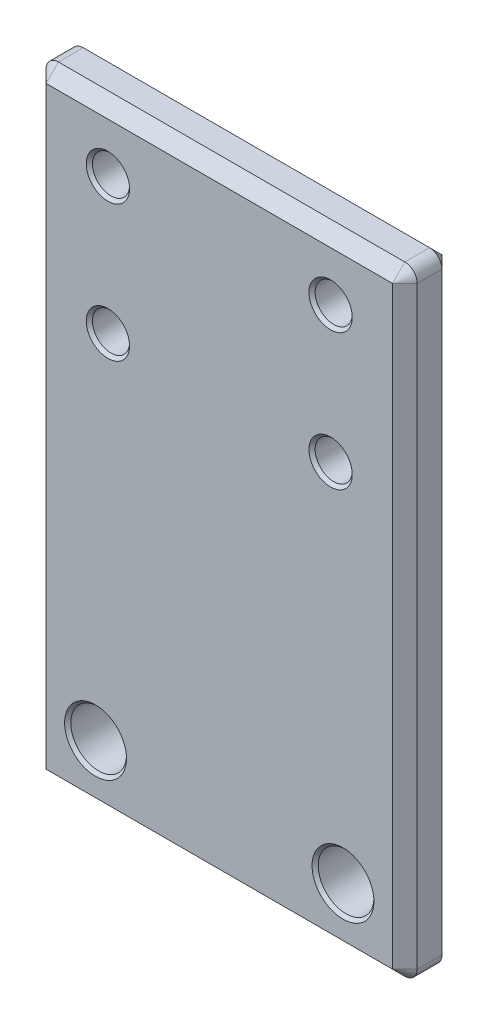
SolidWorks part; units mm, degrees
material "ABS"
ref_plane "Front Plane" through (0, 0, 0) normal (0, 0, 1) x (1, 0, 0)
ref_plane "Top Plane" through (0, 0, 0) normal (0, 1, 0) x (1, 0, 0)
ref_plane "Right Plane" through (0, 0, 0) normal (1, 0, 0) x (0, 0, -1)
ref_axis "X Axis" through (88.99, 0, 0) along (-1, 0, 0)
ref_axis "Y Axis" through (0, 55, 0) along (0, -1, 0)
ref_axis "Z Axis" through (0, 0, -88.99) along (0, 0, 1)
sketch "Sketch1" plane through (0, 0, 0) normal (0, 0, 1) x (1, 0, 0)
  line L1 (-15, -39.5) -> (15, -39.5)
  line L2 (-15, -39.5) -> (-15, 10.5)
  line L3 (-15, 10.5) -> (15, 10.5)
  line L4 (15, -39.5) -> (15, 10.5)
  line L5 (0, 10.5) -> (0, -39.5) construction
  line L6 (-15, -14.5) -> (15, -14.5) construction
  line L7 (9, -5.5) -> (-9, -5.5) construction
  line L8 (9, -5.5) -> (9, 5.5) construction
  line L9 (9, 5.5) -> (-9, 5.5) construction
  line L10 (-9, -5.5) -> (-9, 5.5) construction
  line L11 (0, 5.5) -> (0, -5.5) construction
  line L12 (9, 0) -> (-9, 0) construction
  line L15 (9, 10.5) -> (15, 10.5) construction
  line L16 (15, 5.5) -> (15, 10.5) construction
  line L17 (10, -34.5) -> (-10, -34.5) construction
  line L18 (10, -34.5) -> (10, -39.5) construction
  line L19 (10, -39.5) -> (-10, -39.5) construction
  line L20 (-10, -34.5) -> (-10, -39.5) construction
  line L21 (0, -39.5) -> (0, -34.5) construction
  line L22 (10, -37) -> (-10, -37) construction
  point P0 (0, -14.5)
  point P4 (0, 0)
  point P18 (0, -37)
  dimension "D1" = 50
  dimension "D2" = 30
  dimension "D3" = 11
  dimension "D4" = 18
  dimension "D5" = 5
  dimension "D6" = 20
  dimension "D7" = 5
extrude "Boss-Extrude1" add sketch "Sketch1" along normal blind 4
sketch "Sketch6" plane through (0, 0, 4) normal (0, 0, 1) x (1, 0, 0)
  point P0 (-9, 5.5)
  point P3 (-9, -5.5)
  point P6 (9, -5.5)
  point P9 (9, 5.5)
hole_wizard "Ø3.0mm Dowel Hole1" positions "Sketch6" profile "Sketch5" hole size "Ø3.0" standard "ANSI Metric" end condition through all
sketch "Sketch5" plane through (-9, 5.5, 4) normal (1, 0, 0) x (0, -1, 0)
  line L0 (0, 0) -> (0, 4)
  line L1 (0, 4) -> (1.75, 4)
  line L2 (1.5, 3.75) -> (1.5, 0.25)
  line L3 (1.5, 0.25) -> (1.75, 0)
  line L5 (1.75, 0) -> (0, 0)
  line L6 (-1.5, 0.25) -> (-1.75, 0) construction
  line L7 (1.75, 4) -> (1.5, 3.75)
  line L8 (-1.75, 4) -> (-1.5, 3.75) construction
  line L11 (0, -6.35) -> (0, 107.95) construction
  dimension "Thru Hole Dia." = 3
  dimension "Thru Hole Depth" = 4
  dimension "Near C'Sink Dia." = 3.5
  dimension "Near C'Sink Angle" = 90
  dimension "Far C'Sink Dia." = 3.5
  dimension "Far C'Sink Angle" = 90
sketch "Sketch9" plane through (0, 0, 4) normal (0, 0, 1) x (1, 0, 0)
  point P0 (-10, -34.5)
  point P3 (10, -34.5)
hole_wizard "M4 Clearance Hole1" positions "Sketch9" profile "Sketch8" hole size "M4" standard "ANSI Metric" end condition through all
sketch "Sketch8" plane through (-10, -34.5, 4) normal (1, 0, 0) x (0, -1, 0)
  line L0 (0, 0) -> (0, 4)
  line L1 (0, 4) -> (2.5, 4)
  line L2 (2.25, 3.75) -> (2.25, 0.25)
  line L3 (2.25, 0.25) -> (2.5, 0)
  line L5 (2.5, 0) -> (0, 0)
  line L6 (-2.25, 0.25) -> (-2.5, 0) construction
  line L7 (2.5, 4) -> (2.25, 3.75)
  line L8 (-2.5, 4) -> (-2.25, 3.75) construction
  line L11 (0, -6.35) -> (0, 107.95) construction
  dimension "Thru Hole Dia." = 4.5
  dimension "Thru Hole Depth" = 4
  dimension "Near C'Sink Dia." = 5
  dimension "Near C'Sink Angle" = 90
  dimension "Far C'Sink Dia." = 5
  dimension "Far C'Sink Angle" = 90
fillet "Fillet1" radius 1 4 edges at (15, 10.5, 2) (15, -39.5, 2) (-15, -39.5, 2) (-15, 10.5, 2)
chamfer "Chamfer1" distance 1 angle 45 16 edges at (0, -39.5, 0) (14.7071, -39.2071, 0) (-14.7071, -39.2071, 0) (15, -14.5, 0) (-15, -14.5, 0) (14.7071, 10.2071, 0) (-14.7071, 10.2071, 0) (0, 10.5, 0) (0, -39.5, 4) (14.7071, -39.2071, 4) (-14.7071, -39.2071, 4) (15, -14.5, 4) (-15, -14.5, 4) (14.7071, 10.2071, 4) (-14.7071, 10.2071, 4) (0, 10.5, 4)
